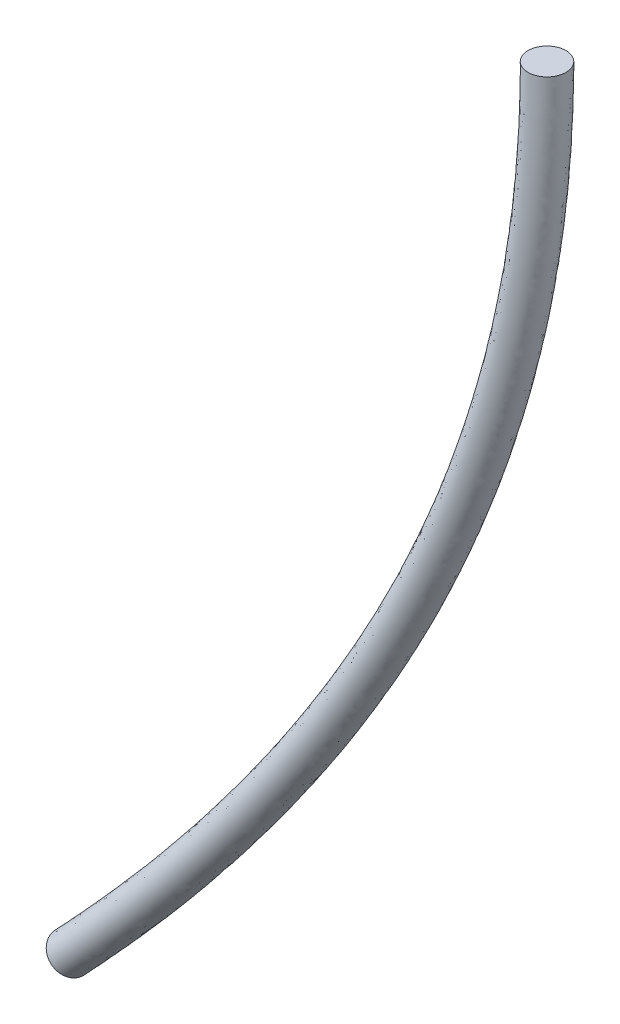
SolidWorks part; units mm, degrees
material "AISI 304"
ref_plane "Front Plane" through (0, 0, 0) normal (0, 0, 1) x (1, 0, 0)
ref_plane "Top Plane" through (0, 0, 0) normal (0, 1, 0) x (1, 0, 0)
ref_plane "Right Plane" through (0, 0, 0) normal (1, 0, 0) x (0, 0, -1)
sketch "Sketch4" plane through (0, 0, 0) normal (0, 1, 0) x (1, 0, 0)
  circle A0 centre (0, 0) radius 1.5
  dimension "D1" = 3
sketch "Sketch5" plane through (0, 0, 0) normal (0, 0, 1) x (1, 0, 0)
  line L0 (1.5, 0) -> (-1.5, 0) construction
  line L1 (0, 0) -> (0, -80) construction
  line L2 (0, 0) -> (0, -40) construction
  line L3 (0, -40) -> (-37.7967, -80) construction
  line L5 (0, -80) -> (-37.7967, -80) construction
  spline S0 degree 2 poles (0, 0) (0, -40) (-37.7967, -80) knots 0 0 0 1 1 1
  point P5 (-37.7967, -80)
  dimension "D1" = 80
  dimension "D2" = 40
sweep "Sweep1" add profiles "Sketch4" path "Sketch5"
